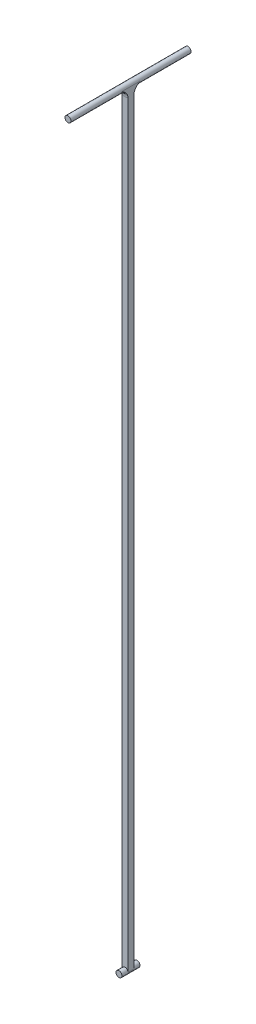
SolidWorks part; units mm, degrees
material "Cast Alloy Steel"
ref_plane "Front Plane" through (0, 0, 0) normal (0, 0, 1) x (1, 0, 0)
ref_plane "Top Plane" through (0, 0, 0) normal (0, 1, 0) x (1, 0, 0)
ref_plane "Right Plane" through (0, 0, 0) normal (1, 0, 0) x (0, 0, -1)
sketch "Sketch1" plane through (0, 0, 0) normal (0, 0, 1) x (1, 0, 0)
  line L1 (0, 0) -> (5.08, 0)
  line L2 (0, 0) -> (0, 647.7)
  line L3 (0, 647.7) -> (5.08, 647.7)
  line L4 (5.08, 0) -> (5.08, 647.7)
  circle A0 centre (2.54, 647.7) radius 2.54
  dimension "D1" = 647.7
  dimension "D2" = 5.08
extrude "Boss-Extrude1" add sketch "Sketch1" along normal mid plane 101.6 contours L3 A0 | L3 A0 region at (2.54, 648.778, 0) region at (2.54, 646.622, 0)
extrude "Boss-Extrude2" add sketch "Sketch1<4>" along normal mid plane 5.08 contours A0 L2 L1 L4 region at (2.54, 322.8528, 0)
sketch "Sketch1<4>" plane through (0, 0, 0) normal (0, 0, 1) x (1, 0, 0) same geometry as "Sketch1"
sketch "Sketch2" plane through (0, 0, 2.54) normal (0, 0, 1) x (1, 0, 0)
  line L0 (0, 0) -> (5.08, 0) construction
  circle A0 centre (2.54, 0) radius 2.54
extrude "Boss-Extrude3" add sketch "Sketch2" along normal blind 5.08
sketch "Sketch4" plane through (0, 0, 7.62) normal (0, 0, 1) x (1, 0, 0)
  circle A1 centre (2.54, 0) radius 2.54
  circle A2 centre (2.54, 0) radius 2.54
  dimension "D1" = 0
extrude "Boss-Extrude4" add sketch "Sketch4" against normal blind 15.24
fillet "Fillet1" radius 5.08 1 edges at (2.54, 645.16, 2.54)
fillet "Fillet2" radius 5.08 1 edges at (2.54, 645.16, -2.54)
